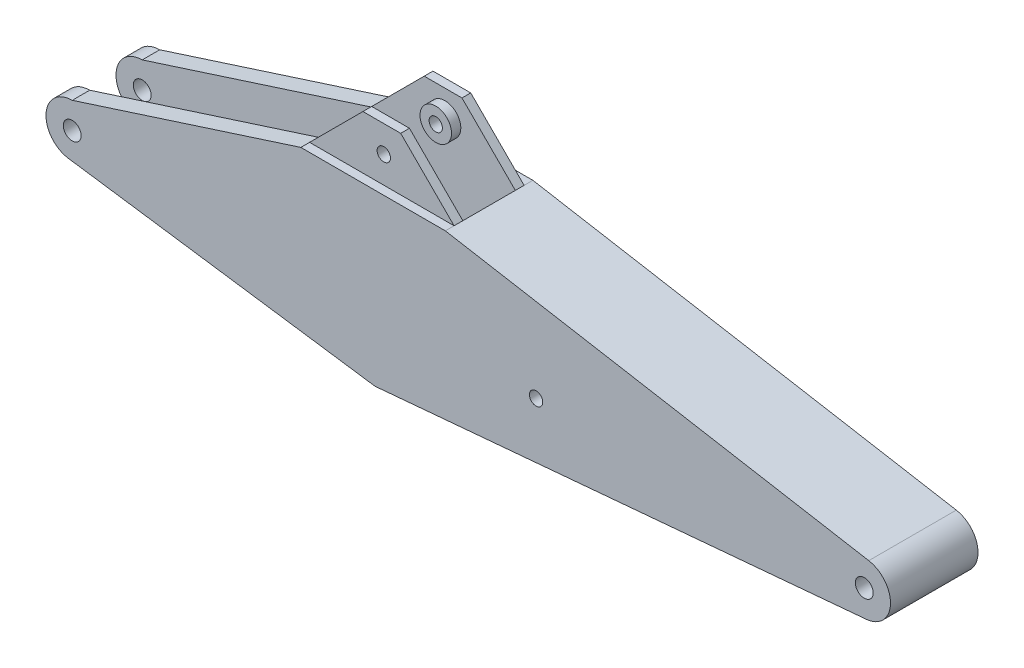
SolidWorks part; units mm, degrees
ref_plane "Front Plane" through (0, 0, 0) normal (0, 0, 1) x (1, 0, 0)
ref_plane "Top Plane" through (0, 0, 0) normal (0, 1, 0) x (1, 0, 0)
ref_plane "Right Plane" through (0, 0, 0) normal (1, 0, 0) x (0, 0, -1)
sketch "Sketch1" plane through (0, 0, 0) normal (0, 0, 1) x (1, 0, 0)
  line L0 (0, 0) -> (4525, 0) construction
  line L1 (1730, 875) -> (1730, -400) construction
  line L2 (1826.7184, 875) -> (1611.0224, 875)
  line L3 (1611.0224, 875) -> (1306.0224, 570)
  line L4 (1306.0224, 570) -> (0, 150)
  line L5 (1730, -400) -> (-21.3241, -148.4765)
  line L6 (1730, -400) -> (4538.3319, -149.4064)
  line L7 (1826.7184, 875) -> (2131.7184, 570)
  line L8 (2131.7184, 570) -> (4550.7916, 147.766)
  line L9 (1306.0224, 570) -> (2131.7184, 570)
  circle A0 centre (0, 0) radius 51
  arc A1 (0, 150) -> (-21.3241, -148.4765) centre (0, 0) ccw
  arc A3 (4538.3319, -149.4064) -> (4550.7916, 147.766) centre (4525, 0) ccw
  circle A4 centre (2650, 0) radius 38
  circle A5 centre (4525, 0) radius 51
  circle A6 centre (1730, 723) radius 38
  dimension "D5" = 300
  dimension "D6" = 102
  dimension "D7" = 76
  dimension "D12" = 76
  dimension "D1" = 4525
  dimension "D2" = 400
  dimension "D3" = 875
  dimension "D4" = 2795
  dimension "D8" = 2650
  dimension "D9" = 15
  dimension "D10" = 26
  dimension "D11" = 305
  dimension "D13" = 153
  dimension "D14" = 45
  dimension "D15" = 45
extrude "Boss-Extrude1" add sketch "Sketch1" along normal blind 100 from offset 150 contours L6 A3 L8 L9 L4 A1 L5 A5 A4 A0 | L3 L9 L7 L2 A6 region at (1972.9943, 716.2759, 0) region at (2154.7038, 70.43, 0)
sketch "Sketch3" plane through (0, 0, 150) normal (0, 0, -1) x (-1, 0, 0)
  line L0 (-1730, -400) -> (-4538.3319, -149.4064) construction
  line L1 (-2131.7184, 570) -> (-4550.7916, 147.766) construction
  line L2 (-1730, -400) -> (-4538.3319, -149.4064)
  line L3 (-2131.7184, 570) -> (-4550.7916, 147.766)
  line L4 (-1730, -400) -> (-706, -252.9341)
  line L5 (-1730, -400) -> (21.3241, -148.4765) construction
  line L6 (-2124.8407, 530.5957) -> (-4543.9139, 108.3617)
  line L7 (-1731.08, -359.7447) -> (-4534.7767, -109.5647)
  line L8 (-1731.08, -359.7447) -> (-711.6864, -213.3404)
  line L9 (-2124.8407, 530.5957) -> (-2131.7184, 570)
  line L10 (-711.6864, -213.3404) -> (-706, -252.9341)
  arc A0 (-4550.7916, 147.766) -> (-4538.3319, -149.4064) centre (-4525, 0) ccw construction
  arc A1 (-4550.7916, 147.766) -> (-4538.3319, -149.4064) centre (-4525, 0) ccw
  arc A2 (-4543.9139, 108.3617) -> (-4534.7767, -109.5647) centre (-4525, 0) ccw
  dimension "D1" = 706
  dimension "D2" = 40
extrude "Boss-Extrude2" add sketch "Sketch3" along normal blind 306
sketch "Sketch4" plane through (0, 0, 150) normal (0, 0, -1) x (-1, 0, 0)
  circle A0 centre (-2650, 0) radius 38 construction
  circle A1 centre (-2650, 0) radius 38
  circle A2 centre (-1730, 723) radius 38 construction
  circle A3 centre (-1730, 723) radius 38
  circle A4 centre (-2650, 0) radius 90
  circle A5 centre (-1730, 723) radius 90
  dimension "D1" = 180
  dimension "D2" = 180
extrude "Boss-Extrude3" add sketch "Sketch4" along normal blind 53
extrude "Cut-Extrude1" cut sketch "Sketch1<3>" against normal blind 50 from surface contours L3 L9 L7 L2 A6 region at (1972.9943, 716.2759, 0) starting at face at (4576, 0, 250)
sketch "Sketch1<3>" plane through (0, 0, 0) normal (0, 0, 1) x (1, 0, 0) same geometry as "Sketch1"
mirror "Mirror1" about plane through (0, 0, 0) normal (0, 0, 1) of "Boss-Extrude3", "Boss-Extrude1"
extrude "Cut-Extrude2" cut sketch "Sketch1<5>" along normal blind 50 from surface contours L3 L9 L7 L2 A6 region at (1972.9943, 716.2759, 0) starting at face at (4576, 0, -250)
sketch "Sketch1<5>" plane through (0, 0, 0) normal (0, 0, 1) x (1, 0, 0) same geometry as "Sketch1"
